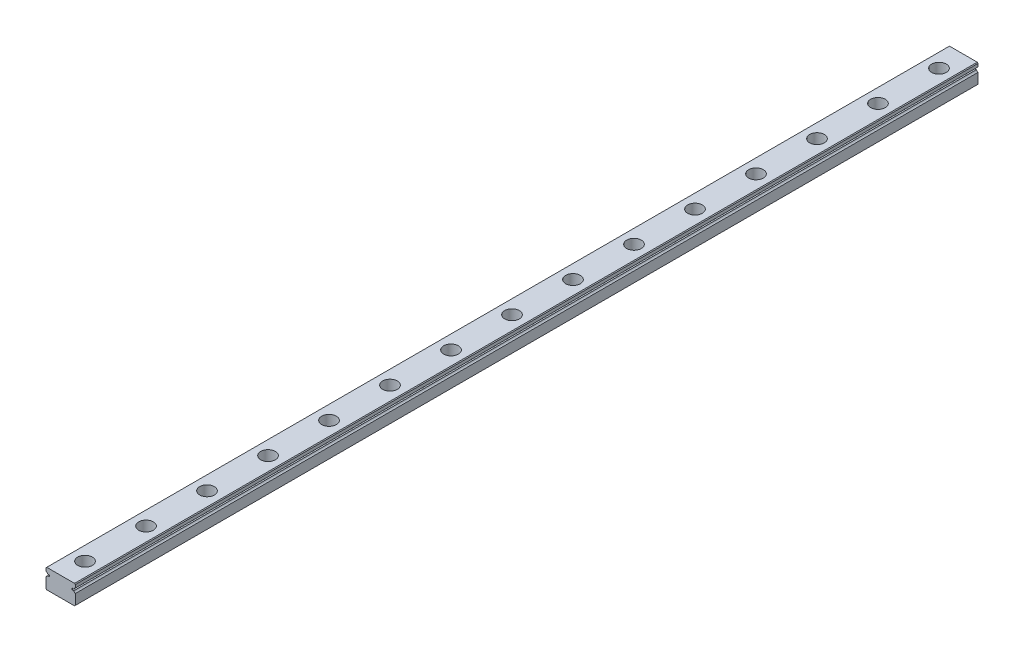
SolidWorks part; units mm, degrees
ref_plane "Спереди" through (0, 0, 0) normal (0, 0, 1) x (1, 0, 0)
ref_plane "Сверху" through (0, 0, 0) normal (0, 1, 0) x (1, 0, 0)
ref_plane "Справа" through (0, 0, 0) normal (1, 0, 0) x (0, 0, -1)
sketch "Эскиз1" plane through (0, 0, 0) normal (0, 0, 1) x (1, 0, 0)
  line L0 (-6, 3.7) -> (-5.7, 4)
  line L1 (-5.7, -4) -> (5.7, -4)
  line L2 (-6, -3.7) -> (-6, 0.549)
  line L3 (-5.7, 4) -> (5.7, 4)
  line L4 (6, -3.7) -> (6, 0.549)
  line L5 (-6, -4) -> (6, 4) construction
  line L6 (-6, 4) -> (6, -4) construction
  line L7 (-6, -3.7) -> (-5.7, -4)
  line L8 (5.7, -4) -> (6, -3.7)
  line L9 (5.7, 4) -> (6, 3.7)
  line L10 (-6, 2.451) -> (-6, 3.7)
  line L11 (-5.3546, 1.7981) -> (-4.6435, 1.7981)
  line L12 (0, 5.4188) -> (0, -5.747) construction
  line L13 (-5.3546, 1.2019) -> (-4.6435, 1.2019)
  line L14 (-4.6435, 1.7981) -> (-4.6435, 1.2019)
  line L15 (4.6435, 1.7981) -> (4.6435, 1.2019)
  line L16 (5.3546, 1.2019) -> (4.6435, 1.2019)
  line L17 (5.3546, 1.7981) -> (4.6435, 1.7981)
  line L18 (6, 2.451) -> (6, 3.7)
  line L19 (4.6435, 1.7981) -> (5.3546, 1.7981) construction
  arc A0 (-6, 0.549) -> (-5.3546, 1.2019) centre (-6.3091, 1.5) ccw
  arc A1 (-5.3546, 1.7981) -> (-6, 2.451) centre (-6.3091, 1.5) ccw
  arc A2 (5.3546, 1.7981) -> (6, 2.451) centre (6.3091, 1.5) cw
  arc A3 (6, 0.549) -> (5.3546, 1.2019) centre (6.3091, 1.5) cw
  point P0 (0, 0)
extrude "Бобышка-Вытянуть1" add sketch "Эскиз1" along normal blind 370
sketch "Эскиз2" plane through (0, 4, 0) normal (0, 1, 0) x (1, 0, 0)
  line L0 (0, 0) -> (0, -26.2396) construction
  line L1 (5.7, 0) -> (-5.7, 0) construction
  line L2 (-3.8306, -10) -> (3.8306, -10) construction
  circle A0 centre (0, -10) radius 3
  circle A1 centre (0, -10) radius 1.75
  dimension "D2" = 3.5
  dimension "D3" = 6
  dimension "D1" = 10
extrude "Вырез-Вытянуть1" cut sketch "Эскиз2" against normal blind 4.5
extrude "Вырез-Вытянуть2" cut sketch "Эскиз2<2>" against normal through all contours A1 region at (0, 4, 10)
sketch "Эскиз2<2>" plane through (0, 4, 0) normal (0, 1, 0) x (1, 0, 0) same geometry as "Эскиз2"
pattern_linear "Линейный массив1" count 16 spacing 25 along (0, 0, 1) of "Вырез-Вытянуть1", "Вырез-Вытянуть2"
